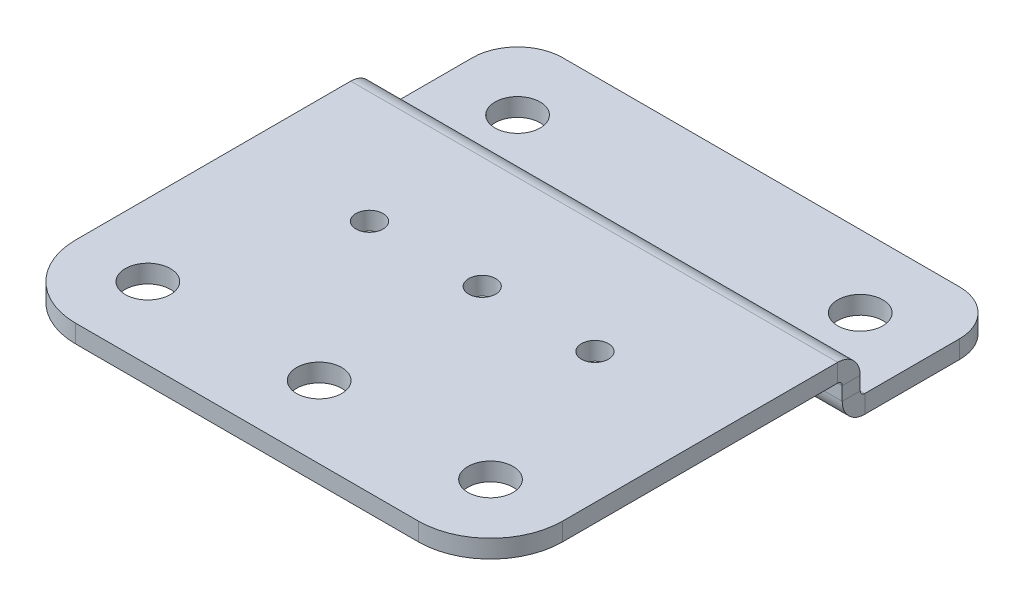
SolidWorks part; units mm, degrees
note: The reader was unsure of these and kept them because the rebuilt part matched: thickness of "Base-Flange1", "Edge-Flange1", "Edge-Flange2", "Sheet-Metal1", "Sheet-Metal2", "Sheet-Metal6", "Sheet-Metal7", "Sheet-Metal8"; flange length of "Edge-Flange1", "Edge-Flange2".
ref_plane "Front Plane" through (0, 0, 0) normal (0, 0, 1) x (1, 0, 0)
ref_plane "Top Plane" through (0, 0, 0) normal (0, 1, 0) x (1, 0, 0)
ref_plane "Right Plane" through (0, 0, 0) normal (1, 0, 0) x (0, 0, -1)
sketch "Sketch1" plane through (0, 0, 0) normal (0, 1, 0) x (1, 0, 0)
  line L0 (27, 16) -> (27, 0) construction
  line L1 (0, 0) -> (54, 0)
  line L2 (0, 0) -> (0, 11)
  line L3 (5, 16) -> (49, 16)
  line L4 (54, 0) -> (54, 11)
  circle A0 centre (8, 8) radius 2.5
  circle A1 centre (46, 8) radius 2.5
  arc A2 (49, 16) -> (54, 11) centre (49, 11) cw
  arc A3 (0, 11) -> (5, 16) centre (5, 11) cw
  point P9 (27, 8)
  point P20 (0, 16)
  dimension "D3" = 19
  dimension "D4" = 5
  dimension "D5" = 5
  dimension "D1" = 16
  dimension "D2" = 54
  dimension "D6" = 8
base flange "Base-Flange1" sketch "Sketch1" thickness 2 reverse thickness direction no parameters "D1"=0.7366
edge flange "Edge-Flange1" sketch "Sketch8" flange angle 90 flange length 4 flange position material outside bend radius 0.5 thickness 2 parameters "D6"=10
sketch "Sketch8" plane through (0, 0, 0) normal (0, 0, 1) x (1, 0, 0)
  line L0 (0, 0) -> (54, 0) construction
  line L1 (0, 0) -> (54, 0)
  line L2 (0, 0) -> (0, 2)
  line L3 (0, 2) -> (54, 2)
  line L4 (54, 2) -> (54, 0)
bend "EdgeBend1" bend radius 0.5 bend angle 90 parameters "D5"=1
sketch "Sketch9" plane through (0, 2, 0) normal (0, 1, 0) x (1, 0, 0)
  line L0 (54, 0) -> (0, 0) construction
  line L1 (54, -2) -> (0, -2) construction
  line L2 (16, 0) -> (38, 0)
  line L3 (16, 0) -> (16, -2)
  line L4 (16, -2) -> (38, -2)
  line L5 (38, 0) -> (38, -2)
  line L6 (27, 0) -> (27, -2) construction
  point P10 (27, 0)
  dimension "D1" = 22
edge flange "Edge-Flange2" sketch "Sketch22" flange angle 90 flange length 41 flange position bend outside bend radius 0.5 thickness 2 parameters "D6"=10
sketch "Sketch22" plane through (0, 2, 2) normal (0, 1, 0) x (-1, 0, 0)
  line L2 (0, 0) -> (0, 39)
  line L3 (0, 39) -> (-54, 39)
  line L4 (-54, 39) -> (-54, 0)
  line L9 (-54, 0) -> (0, 0) construction
  line L10 (-54, 0) -> (0, 0)
bend "EdgeBend2" bend radius 0.5 bend angle 90 parameters "D5"=2
sketch "Sketch25" plane through (0, 4.5, 0) normal (0, 1, 0) x (1, 0, 0)
  line L0 (0, -41) -> (54, -41) construction
  line L1 (27, -41) -> (27, -2.5)
  line L2 (54, -41) -> (54, -2.5) construction
  line L3 (54, -33) -> (46, -33)
  line L9 (54, -2.5) -> (0, -2.5) construction
  line L16 (46, -33) -> (8, -33) construction
  line L17 (54, -33) -> (54, -41)
  line L18 (54, -41) -> (46, -41)
  line L19 (8, -41) -> (0, -41)
  line L20 (0, -41) -> (0, -33)
  circle A0 centre (46, -33) radius 8
  circle A2 centre (46, -33) radius 2.5
  circle A8 centre (8, -33) radius 2.5
  circle A9 centre (8, -33) radius 8
  circle A10 centre (27, -33) radius 2.5
  point P6 (27, -33)
  point P21 (27, -33)
  dimension "D2" = 8
  dimension "D4" = 8
extrude "Cut-Extrude1" cut sketch "Sketch25" against normal through all
sketch "Sketch26" plane through (0, 4.5, 0) normal (0, 1, 0) x (1, 0, 0)
  line L0 (54, -33) -> (54, -2.5) construction
  line L3 (54, -2.5) -> (0, -2.5) construction
  circle A0 centre (39.5, -14.92) radius 1.5
  circle A1 centre (27, -14.92) radius 1.5
  circle A2 centre (14.5, -14.92) radius 1.5
  dimension "D1" = 3
  dimension "D2" = 14.5
  dimension "D3" = 12.42
extrude "Cut-Extrude2" cut sketch "Sketch26" along direction (0, 1, 0) on the side against the normal up to next (2 mm away)
sketch "Bend-Lines1" [suppressed] plane through (0, 0, 0) normal (0, 1, 0) x (1, 0, 0)
sketch "Bounding-Box1" [suppressed] plane through (0, 0, 0) normal (0, 1, 0) x (1, 0, 0)
sheet metal parameters "Sheet-Metal1" thickness 2 parameters "D1"=0.7366
flat pattern "Flat-Pattern1" [suppressed]
sketch "Bend-Lines2" plane through (0, 0, 0) normal (0, 1, 0) x (1, 0, 0)
sketch3d "Bounding-Box2" [suppressed]
  line L0 (6, 6, 0) -> (-48, 6, 0) construction
  line L1 (6, -10, 0) -> (-48, -10, 0) construction
  line L2 (6, 6, 0) -> (6, -10, 0) construction
  line L3 (-48, 6, 0) -> (-48, -10, 0) construction
sheet metal parameters "Sheet-Metal2" thickness 2 parameters "D1"=0.7366, "D7"=3
flat pattern "Flat-Pattern1" [suppressed]
sketch "Bend-Lines2" plane through (0, 0, 0) normal (0, 1, 0) x (1, 0, 0)
  line L0 (0, -0.8352) -> (54, -0.8352) construction
  line L1 (0, -0.8352) -> (54, -0.8352) construction
sketch3d "Bounding-Box2" [suppressed]
  line L0 (-5, 5, 0) -> (49, 5, 0) construction
  line L1 (-5, -13.6704, 0) -> (49, -13.6703, 0) construction
  line L2 (-5, 5, 0) -> (-5, -13.6704, 0) construction
  line L3 (49, 5, 0) -> (49, -13.6703, 0) construction
bend of the flat pattern "Flatten-<EdgeBend1>1"
sketch "Sketch13-1" [suppressed] plane through (0, -3, 1.6704) normal (0, -1, 0) x (1, 0, 0)
  line L0 (16, 24) -> (38, 24)
  line L1 (8, 16) -> (46, 16) construction
  line L3 (16, 8) -> (38, 8)
  line L5 (16, 24) -> (16, 8)
  line L6 (38, 24) -> (38, 8)
  circle A0 centre (27, 16) radius 2.5
  dimension "D1" = 8
sketch "Sketch10-3" [suppressed] plane through (0, -3, 1.6704) normal (0, -1, 0) x (1, 0, 0)
  line L1 (54, 1) -> (0, 1) construction
  line L6 (54, 16) -> (54, 1)
  line L8 (38, 16) -> (0, 1)
  line L9 (16, 16) -> (54, 1)
  line L11 (0, 1) -> (0, 16)
  line L12 (8, 16) -> (46, 16) construction
  line L13 (0, 1) -> (54, 1)
  line L14 (16, 8) -> (38, 8)
  line L15 (54, 1) -> (0, 1)
  line L16 (16, 16) -> (16, 8)
  line L17 (38, 16) -> (38, 8)
  line L18 (0, 1) -> (8, 24)
  line L19 (46, 24) -> (54, 1)
  circle A0 centre (8, 16) radius 2.5
  circle A1 centre (46, 16) radius 2.5
  arc A2 (0, 16) -> (16, 16) centre (8, 16) cw
  arc A3 (38, 16) -> (54, 16) centre (46, 16) cw
  circle A4 centre (27, 16) radius 2.5
  dimension "D1" = 24.3516
  dimension "D2" = 5
  dimension "D3" = 5
  dimension "D5" = 8
  dimension "D6" = 8
  dimension "D4" = 15
  dimension "D7" = 8
sheet metal parameters "Sheet-Metal6" thickness 2 parameters "D1"=0.7366, "D7"=3
flat pattern "Flat-Pattern1" [suppressed]
sketch "Bend-Lines2" plane through (0, 0, 0) normal (0, 1, 0) x (1, 0, 0)
  line L0 (0, -0.8352) -> (54, -0.8352) construction
  line L1 (0, -0.8352) -> (54, -0.8352) construction
  line L2 (0, -4.0055) -> (54, -4.0055) construction
  line L3 (0, -4.0055) -> (54, -4.0055) construction
sketch3d "Bounding-Box2" [suppressed]
  line L0 (-5, 5, 0) -> (49, 5, 0) construction
  line L1 (-5, -37.8407, 0) -> (49, -37.8407, 0) construction
  line L2 (-5, 5, 0) -> (-5, -37.8407, 0) construction
  line L3 (49, 5, 0) -> (49, -37.8407, 0) construction
bend of the flat pattern "Flatten-<EdgeBend1>1"
sketch "Sketch13-1" [suppressed] plane through (0, -3, 1.6704) normal (0, -1, 0) x (1, 0, 0)
  line L0 (16, 24) -> (38, 24)
  line L1 (8, 16) -> (46, 16) construction
  line L3 (16, 8) -> (38, 8)
  line L5 (16, 24) -> (16, 8)
  line L6 (38, 24) -> (38, 8)
  circle A0 centre (27, 16) radius 2.5
  dimension "D1" = 8
sketch "Sketch10-3" [suppressed] plane through (0, -3, 1.6704) normal (0, -1, 0) x (1, 0, 0)
  line L1 (54, 1) -> (0, 1) construction
  line L6 (54, 16) -> (54, 1)
  line L8 (38, 16) -> (0, 1)
  line L9 (16, 16) -> (54, 1)
  line L11 (0, 1) -> (0, 16)
  line L12 (8, 16) -> (46, 16) construction
  line L13 (0, 1) -> (54, 1)
  line L14 (16, 8) -> (38, 8)
  line L15 (54, 1) -> (0, 1)
  line L16 (16, 16) -> (16, 8)
  line L17 (38, 16) -> (38, 8)
  line L18 (0, 1) -> (8, 24)
  line L19 (46, 24) -> (54, 1)
  circle A0 centre (8, 16) radius 2.5
  circle A1 centre (46, 16) radius 2.5
  arc A2 (0, 16) -> (16, 16) centre (8, 16) cw
  arc A3 (38, 16) -> (54, 16) centre (46, 16) cw
  circle A4 centre (27, 16) radius 2.5
  dimension "D1" = 24.3516
  dimension "D2" = 5
  dimension "D3" = 5
  dimension "D5" = 8
  dimension "D6" = 8
  dimension "D4" = 15
  dimension "D7" = 8
bend of the flat pattern "Flatten-<EdgeBend2>1"
sheet metal parameters "Sheet-Metal7" thickness 2 parameters "D1"=0.7366, "D7"=3
flat pattern "Flat-Pattern1" [suppressed]
sketch "Bend-Lines2" plane through (0, 2.5, 0) normal (0, -1, 0) x (-1, 0, 0)
sketch3d "Bounding-Box2" [suppressed]
  line L0 (-16.0497, -25.0502, 0) -> (-0.0502, -24.9502, 0) construction
  line L1 (-15.9497, -41.0497, 0) -> (0.0498, -40.9497, 0) construction
  line L2 (-16.0497, -25.0502, 0) -> (-15.9497, -41.0497, 0) construction
  line L3 (-0.0502, -24.9502, 0) -> (0.0498, -40.9497, 0) construction
bend of the flat pattern "Flatten-<EdgeBend1>1"
bend of the flat pattern "Flatten-<EdgeBend2>1"
sheet metal parameters "Sheet-Metal8" thickness 2 parameters "D1"=0.7366, "D7"=3
flat pattern "Flat-Pattern1"
sketch "Bend-Lines2" plane through (0, 2.5, 0) normal (0, -1, 0) x (-1, 0, 0)
  line L0 (-54, -1.479) -> (0, -1.479) construction
  line L1 (-54, 2.0631) -> (0, 2.0631) construction
  line L2 (-54, -1.479) -> (0, -1.479) construction
  line L3 (-54, 2.0631) -> (0, 2.0631) construction
sketch3d "Bounding-Box2" [suppressed]
  line L0 (-54, -41, 0) -> (-54, 18.5841, 0) construction
  line L1 (0, -41, 0) -> (0, 18.5841, 0) construction
  line L2 (-54, -41, 0) -> (0, -41, 0) construction
  line L3 (-54, 18.5841, 0) -> (0, 18.5841, 0) construction
bend of the flat pattern "Flatten-<EdgeBend1>1"
bend of the flat pattern "Flatten-<EdgeBend2>1"
